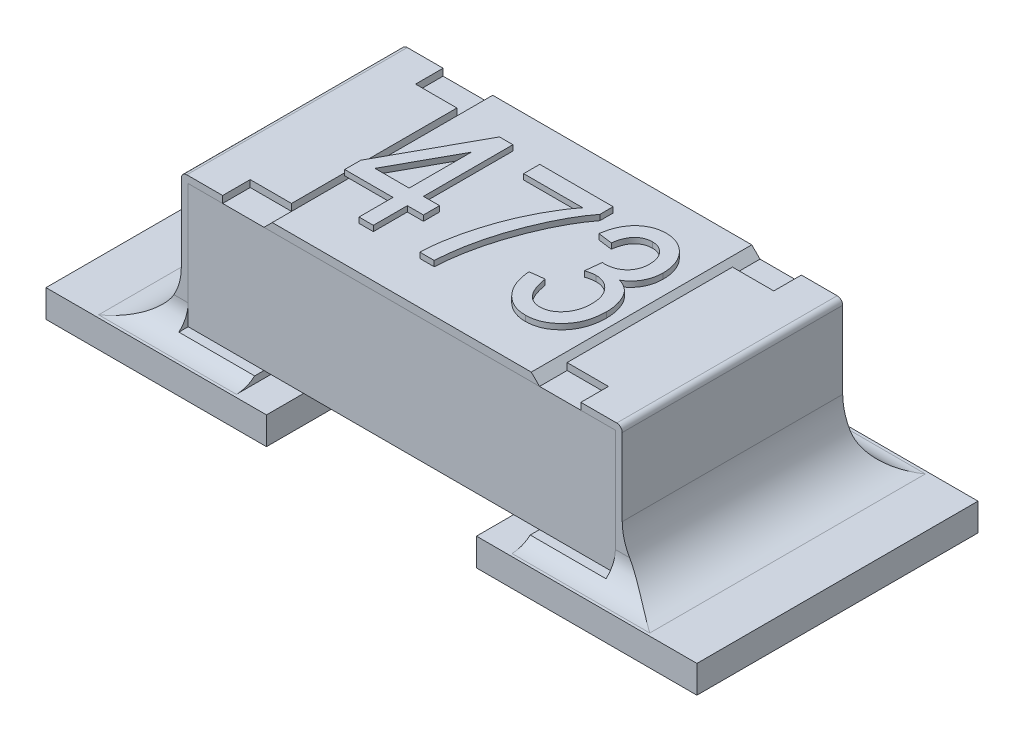
SolidWorks part; units mm, degrees
material "Ceramic Porcelain"
ref_plane "Front Plane" through (0, 0, 0) normal (0, 0, 1) x (1, 0, 0)
ref_plane "Top Plane" through (0, 0, 0) normal (0, 1, 0) x (1, 0, 0)
ref_plane "Right Plane" through (0, 0, 0) normal (1, 0, 0) x (0, 0, -1)
sketch "Sketch1" plane through (0, 0, 0) normal (1, 0, 0) x (0, 0, -1)
  line L0 (0, 55) -> (0, -55) construction
  line L1 (-0.4, 0.575) -> (0.4, 0.575)
  line L2 (-0.4, 0.575) -> (-0.4, 0.125)
  line L3 (-0.4, 0.125) -> (0.4, 0.125)
  line L4 (0.4, 0.575) -> (0.4, 0.125)
  line L5 (55, 0) -> (-55, 0) construction
  dimension "D1" = 0.8
  dimension "D2" = 0.4
  dimension "D3" = 0.45
  dimension "D4" = 0.125
extrude "Boss-Extrude1" add sketch "Sketch1" along normal mid plane 1.55
sketch "Sketch2" plane through (0, 0, 0) normal (0, 0, 1) x (1, 0, 0)
  line L0 (-0.5, 0.6) -> (-0.78, 0.6)
  line L1 (-0.8, 0.58) -> (-0.8, 0.1)
  line L2 (-0.8, 0.1) -> (-0.5, 0.1)
  line L3 (-0.5, 0.1) -> (-0.5, 0.125)
  line L4 (0.775, 0.125) -> (-0.775, 0.125) construction
  line L5 (-0.5, 0.125) -> (-0.775, 0.125)
  line L6 (-0.775, 0.125) -> (-0.775, 0.575)
  line L7 (-0.775, 0.575) -> (-0.5, 0.575)
  line L8 (0.775, 0.575) -> (-0.775, 0.575) construction
  line L9 (-0.5, 0.575) -> (-0.5, 0.6)
  line L11 (0.5, 0.575) -> (0.5, 0.6)
  line L12 (0.5, 0.6) -> (0.78, 0.6)
  line L13 (0.8, 0.58) -> (0.8, 0.1)
  line L14 (0.8, 0.1) -> (0.5, 0.1)
  line L15 (0.5, 0.1) -> (0.5, 0.125)
  line L16 (0.5, 0.125) -> (0.775, 0.125)
  line L17 (0.775, 0.125) -> (0.775, 0.575)
  line L18 (0.775, 0.575) -> (0.5, 0.575)
  arc A0 (0.78, 0.6) -> (0.8, 0.58) centre (0.78, 0.58) cw
  arc A1 (-0.78, 0.6) -> (-0.8, 0.58) centre (-0.78, 0.58) ccw
  point P28 (-0.8, 0.6)
  dimension "D6" = 0.02
  dimension "D1" = 0.025
  dimension "D2" = 0.025
  dimension "D3" = 0.025
  dimension "D4" = 0.3
  dimension "D5" = 0.3
extrude "Boss-Extrude2" add sketch "Sketch2" along normal mid plane 0.8 separate body
sketch "Sketch3" plane through (0, 0.6, 0) normal (0, 1, 0) x (1, 0, 0)
  line L0 (0.5, -0.4) -> (0.5, 0.4) construction
  line L1 (-0.5, 0.4) -> (-0.65, 0.4)
  line L2 (-0.5, 0.4) -> (-0.5, 0.3)
  line L3 (-0.5, 0.3) -> (-0.65, 0.3)
  line L4 (-0.65, 0.4) -> (-0.65, 0.3)
  line L5 (-0.5, -0.4) -> (-0.65, -0.4)
  line L6 (-0.5, -0.4) -> (-0.5, -0.3)
  line L7 (-0.5, -0.3) -> (-0.65, -0.3)
  line L8 (-0.65, -0.4) -> (-0.65, -0.3)
  line L9 (0.5, -0.4) -> (0.65, -0.4)
  line L10 (0.5, -0.4) -> (0.5, -0.3)
  line L11 (0.5, -0.3) -> (0.65, -0.3)
  line L12 (0.65, -0.4) -> (0.65, -0.3)
  line L13 (0.775, -0.4) -> (-0.775, -0.4) construction
  line L15 (0.5, 0.4) -> (0.65, 0.4)
  line L16 (0.5, 0.4) -> (0.5, 0.3)
  line L17 (0.5, 0.3) -> (0.65, 0.3)
  line L18 (0.65, 0.4) -> (0.65, 0.3)
  dimension "D1" = 0.15
  dimension "D2" = 0.1
extrude "Cut-Extrude1" cut sketch "Sketch3" against normal blind 0.025
sketch "Sketch4" plane through (0, 0, 0) normal (0, 0, 1) x (1, 0, 0)
  line L0 (-0.5, 0.575) -> (0.5, 0.575)
  line L1 (0.5, 0.575) -> (0.47, 0.605)
  line L2 (0.47, 0.605) -> (-0.47, 0.605)
  line L3 (-0.47, 0.605) -> (-0.5, 0.575)
  dimension "D1" = 45
  dimension "D2" = 45
  dimension "D3" = 0.03
extrude "Boss-Extrude3" add sketch "Sketch4" along normal mid plane 0.8 separate body
sketch "Sketch7" plane through (0, 0, 0) normal (0, 1, 0) x (1, 0, 0)
  line L0 (0, -0.2833) -> (0, 0.2833) construction
  line L1 (-0.381, -0.51) -> (-1.181, -0.51)
  line L2 (-0.381, -0.51) -> (-0.381, 0.51)
  line L3 (-0.381, 0.51) -> (-1.181, 0.51)
  line L4 (-1.181, -0.51) -> (-1.181, 0.51)
  line L5 (0.381, -0.51) -> (1.181, -0.51)
  line L6 (0.381, -0.51) -> (0.381, 0.51)
  line L7 (0.381, 0.51) -> (1.181, 0.51)
  line L8 (1.181, -0.51) -> (1.181, 0.51)
  line L9 (-0.2833, 0) -> (0.2833, 0) construction
  dimension "D1" = 0.8
  dimension "D2" = 0.381
  dimension "D3" = 0.381
  dimension "D4" = 1.02
  dimension "D5" = 0.51
extrude "Boss-Extrude5" add sketch "Sketch7" along normal blind 0.1
fillet "Fillet3" radius 0.2 1 edges at (-0.8, 0.1, 0)
fillet "Fillet4" radius 0.2 1 edges at (0.8, 0.1, 0)
fillet "Fillet5" radius 0.1 2 edges at (0.75, 0.1, -0.4) (0.75, 0.1, 0.4)
fillet "Fillet6" radius 0.1 2 edges at (-0.75, 0.1, 0.4) (-0.75, 0.1, -0.4)
sketch "Esquisse2" plane through (0, 0.605, 0) normal (0, 1, 0) x (1, 0, 0)
  text T0 "473" font "Arial Narrow" height 0.5
extrude "Boss.-Extru.1" add sketch "Esquisse2" along normal blind 0.02
